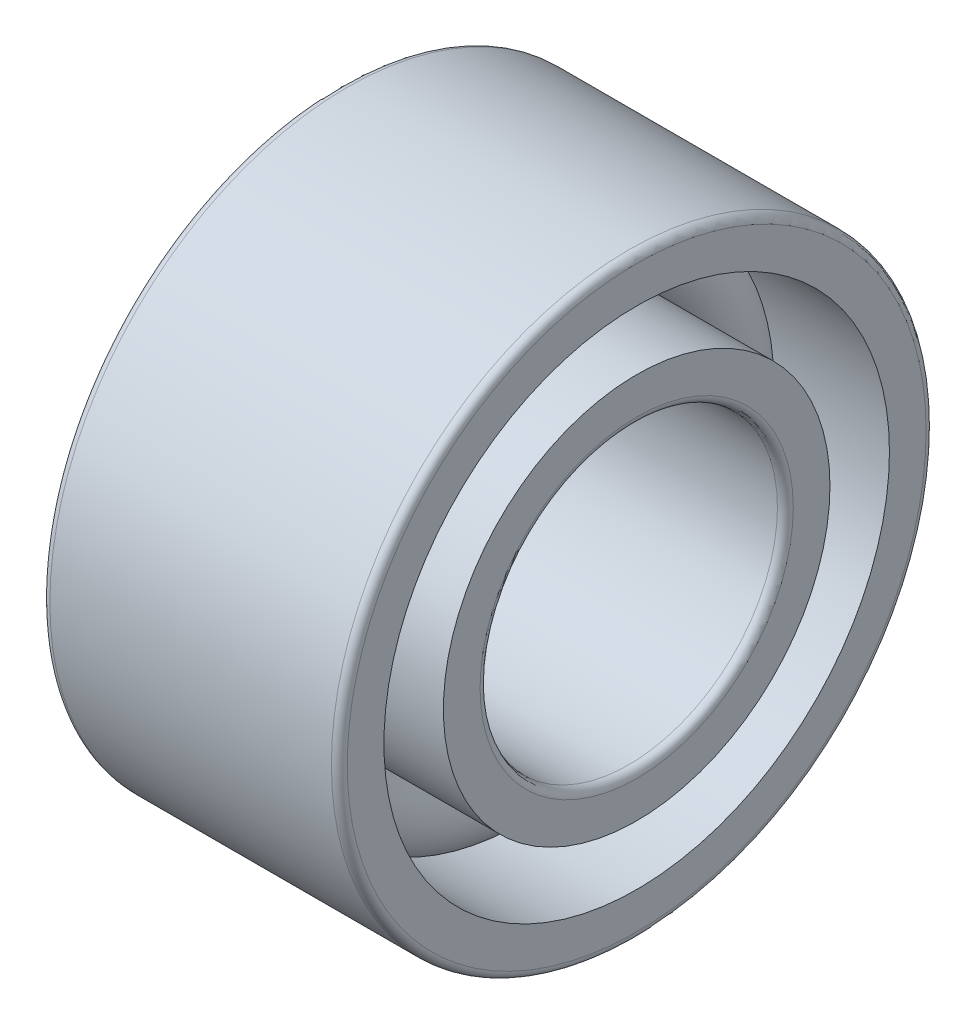
SolidWorks part; units mm, degrees
ref_plane "Plane1" through (0, 0, 0) normal (0, 0, 1) x (1, 0, 0)
ref_plane "Plane2" through (0, 0, 0) normal (0, 1, 0) x (1, 0, 0)
ref_plane "Plane3" through (0, 0, 0) normal (1, 0, 0) x (0, 0, -1)
other "Configuration Table"
sketch "Clipboard" plane through (0, 0, 0) normal (0, 0, 1) x (1, 0, 0)
  line L0 (-10, 0) -> (10, 0) construction
  line L1 (0, 0) -> (22.3471, -0.7804)
  line L2 (0, 0) -> (2.2486, 0.0785)
  line L3 (0, 0) -> (22.3471, -0.7804)
  line L4 (0, 0) -> (-22.3573, -0.3902)
  dimension "BallCLRad" = 2.25
sketch "CagSpiSke" plane through (0, 0, 0) normal (0, 0, 1) x (1, 0, 0)
  line L0 (0.045, 2.175) -> (0.045, 2.325)
  line L1 (0.045, 2.325) -> (-0.045, 2.325)
  line L2 (-0.045, 2.325) -> (-0.045, 2.175)
  line L3 (-0.045, 2.175) -> (0.045, 2.175)
  line L4 (-20.6375, 0) -> (20.6375, 0) construction
  line L5 (0, 0) -> (0, 23.7692) construction
  dimension "OD" = 4.65
  dimension "ID" = 4.35
revolve "CageSpine" add sketch "CagSpiSke" angle 0.001 about L4 reverse direction yes
ref_axis "Axis1" through (-50, 0, 0) along (1, 0, 0)
sketch "CagBalSke" plane through (0, 0, 0) normal (0, 0, 1) x (1, 0, 0)
  line L0 (-0.495, 2.25) -> (0.495, 2.25)
  line L1 (-1.905, 2.25) -> (1.905, 2.25) construction
  line L2 (-10, 0) -> (10, 0) construction
  line L3 (0, 0) -> (0, 24) construction
  arc A0 (0.495, 2.25) -> (-0.495, 2.25) centre (0, 2.25) cw
  dimension "BallCLRad" = 2.25
revolve "CageBall" [suppressed] add sketch "CagBalSke" angle 360 about L1 reverse direction yes
pattern_circular "CageBalls" [suppressed] count 2 every 180 about axis through (-50, 0, 0) along (1, 0, 0)
sketch "CagTrmODSke" plane through (0, 0, 0) normal (0, 0, 1) x (1, 0, 0)
  line L0 (0.496, 2.325) -> (0.496, 2.746)
  line L1 (0.496, 2.746) -> (-0.496, 2.746)
  line L2 (-0.496, 2.746) -> (-0.496, 2.325)
  line L3 (-0.496, 2.325) -> (0.496, 2.325)
  line L4 (-20.6375, 0) -> (20.6375, 0) construction
  line L5 (0, 0) -> (0, 25) construction
  dimension "Width" = 0.992
  dimension "ID" = 4.65
  dimension "OD" = 5.492
revolve "CageTrimOD" [suppressed] cut sketch "CagTrmODSke" angle 360 about L4 reverse direction yes
sketch "CagTrmIDSke" plane through (0, 0, 0) normal (0, 0, 1) x (1, 0, 0)
  line L0 (0.496, 1.756) -> (0.496, 2.175)
  line L1 (0.496, 2.175) -> (-0.496, 2.175)
  line L2 (-0.496, 2.175) -> (-0.496, 1.756)
  line L3 (-0.496, 1.756) -> (0.496, 1.756)
  line L4 (-20.6375, 0) -> (20.6375, 0) construction
  line L5 (0, 0) -> (0, 25) construction
  dimension "Width" = 0.992
  dimension "ID" = 3.512
  dimension "OD" = 4.35
revolve "CageTrimID" [suppressed] cut sketch "CagTrmIDSke" angle 360 about L4 reverse direction yes
sketch "BalSimSke" plane through (0, 0, 0) normal (0, 0, 1) x (1, 0, 0)
  line L0 (-10, 0) -> (10, 0) construction
  line L1 (-10, 2.25) -> (10, 2.25) construction
  line L2 (0, 0) -> (0, 23) construction
  circle A0 centre (0, 2.25) radius 0.45
  dimension "BallCLRad" = 2.25
  dimension "Ball_diameter" = 0.9
revolve "BallsSimplified" add sketch "BalSimSke" angle 360 about L0
sketch "BalDetSke" plane through (0, 0, 0) normal (0, 0, 1) x (1, 0, 0)
  line L0 (-0.45, 2.25) -> (0.45, 2.25)
  line L1 (-1.905, 2.25) -> (1.905, 2.25) construction
  line L2 (0, 0) -> (0, 25) construction
  arc A0 (0.45, 2.25) -> (-0.45, 2.25) centre (0, 2.25) cw
  dimension "BallCLRad" = 2.25
  dimension "Ball_diameter" = 0.9
revolve "BallDetailed" [suppressed] add sketch "BalDetSke" angle 360 about L1 reverse direction yes
sketch "InnRacSke" plane through (0, 0, 0) normal (0, 0, 1) x (1, 0, 0)
  line L0 (-0.301, 1.95) -> (-1.5, 1.95)
  line L1 (-1.5, 1.95) -> (-1.5, 1.58)
  line L2 (-1.42, 1.5) -> (1.42, 1.5)
  line L3 (1.5, 1.58) -> (1.5, 1.95)
  line L4 (1.5, 1.95) -> (0.301, 1.95)
  line L5 (-20.6375, 0) -> (20.6375, 0) construction
  line L6 (0, 0) -> (0, 30) construction
  arc A0 (-1.5, 1.58) -> (-1.42, 1.5) centre (-1.42, 1.58) ccw
  arc A1 (1.42, 1.5) -> (1.5, 1.58) centre (1.42, 1.58) ccw
  arc A2 (0.301, 1.95) -> (-0.301, 1.95) centre (0, 2.25) cw
  dimension "BallCLRad" = 2.25
  dimension "Fillet_radius" = 0.08
  dimension "Ball_diameter" = 0.85
  dimension "ID" = 3
  dimension "OD" = 3.9
  dimension "Width" = 3
revolve "InnerRace" add sketch "InnRacSke" angle 360 about L5 reverse direction yes
sketch "OutRacSke" plane through (0, 0, 0) normal (0, 0, 1) x (1, 0, 0)
  line L0 (-0.301, 2.55) -> (-1.5, 2.55)
  line L1 (-1.5, 2.55) -> (-1.5, 2.92)
  line L2 (-1.42, 3) -> (1.42, 3)
  line L3 (1.5, 2.92) -> (1.5, 2.55)
  line L4 (1.5, 2.55) -> (0.301, 2.55)
  line L5 (-20.6375, 0) -> (20.6375, 0) construction
  line L6 (0, 0) -> (0, 30) construction
  arc A0 (-1.5, 2.92) -> (-1.42, 3) centre (-1.42, 2.92) cw
  arc A1 (1.42, 3) -> (1.5, 2.92) centre (1.42, 2.92) cw
  arc A2 (0.301, 2.55) -> (-0.301, 2.55) centre (0, 2.25) ccw
  dimension "BallCLRad" = 2.25
  dimension "Fillet_radius" = 0.08
  dimension "Ball_diameter" = 0.85
  dimension "Width" = 3
revolve "OuterRace" add sketch "OutRacSke" angle 360 about L5 reverse direction yes
pattern_circular "BallsDetailed" [suppressed] count 2 every 180 about axis through (-50, 0, 0) along (1, 0, 0)
equation "\"BallCLRad@Clipboard\" = ( \"OD@OutRacSke\" + \"ID@InnRacSke\" ) / 4"
equation "\"BallCLRad@BalSimSke\" = \"BallCLRad@Clipboard\""
equation "\"BallCLRad@BalDetSke\" = \"BallCLRad@Clipboard\""
equation "\"BallCLRad@InnRacSke\" = \"BallCLRad@Clipboard\""
equation "\"BallCLRad@OutRacSke\" = \"BallCLRad@Clipboard\""
equation "\"Ball_diameter@InnRacSke\" = \"Ball_diameter@BalDetSke\" - 0.05"
equation "\"Ball_diameter@OutRacSke\" = \"Ball_diameter@BalDetSke\" - 0.05"
equation "\"Ball_diameter@BalSimSke\" = \"Ball_diameter@BalDetSke\""
equation "\"Width@OutRacSke\" = \"Width@InnRacSke\""
equation "\"Fillet_radius@OutRacSke\" = \"Fillet_radius@InnRacSke\""
equation "\"Max_count@Clipboard\" = int( 3.14159265 / atn(( \"Ball_diameter@BalDetSke\" / 2) / sqr( \"BallCLRad@Clipboard\"  *  \"BallCLRad@Clipboard\" - ( \"Ball_diameter@BalDetSke\" / 2) *  ( \"Ball_diameter@BalDetSke\" / 2))))"
equation "\"Max_count@Clipboard\" = ((sgn( \"Max_count@Clipboard\" - \"Count@Clipboard\" )-1)*( \"Max_count@Clipboard\" - \"Count@Clipboard\" ))/-2+ \"Count@Clipboard\""
equation "\"Count@BallsDetailed\" = int( \"Show_count@Clipboard\" ) "
equation "\"Count@BallsDetailed\" = ((sgn( \"Count@BallsDetailed\" - \"Max_count@Clipboard\" )-1)*( \"Count@BallsDetailed\" - \"Max_count@Clipboard\" ))/-2+ \"Max_count@Clipboard\""
equation "\"Count@BallsDetailed\" = ((sgn( \"Count@BallsDetailed\" - \"Min_count@Clipboard\" )+1)*( \"Count@BallsDetailed\" - \"Min_count@Clipboard\"))/2 +\"Min_count@Clipboard\""
equation "\"Angle@BallsDetailed\" = 360.0 / \"Max_count@Clipboard\""
equation "\"BallCLRad@CagBalSke\" = \"BallCLRad@Clipboard\""
equation "\"Count@CageBalls\" = \"Count@BallsDetailed\""
equation "\"Angle@CageBalls\" = \"Angle@BallsDetailed\""
equation "\"Angle@CageSpine\" =  \"Angle@CageBalls\" * ( \"Count@CageBalls\" -1 + int( \"Count@CageBalls\" / \"Max_count@Clipboard\" ) )  + 0.001 -  int( \"Count@CageBalls\" / \"Max_count@Clipboard\" ) * 0.001"
equation "\"Angle@CageSpine\" =  \"Angle@CageSpine\" * int( \"Min_count@Clipboard\" / 2) + int(1 / \"Min_count@Clipboard\")  * 0.001"
equation "\"CageWallOD@CagBalSke\" =  \"Ball_diameter@BalDetSke\" * 1.1"
equation "\"Thickness@CagSpiSke\" =  \"Ball_diameter@BalDetSke\" * 0.1"
equation "\"OD@CagTrmODSke\" = \"BallCLRad@Clipboard\" * 2 + \"CageWallOD@CagBalSke\" + 0.002"
equation "\"ID@CagTrmODSke\" = \"BallCLRad@Clipboard\" * 2 + \"Ball_diameter@BalDetSke\" / 6"
equation "\"OD@CagTrmIDSke\" = \"BallCLRad@Clipboard\" * 2 - \"Ball_diameter@BalDetSke\" / 6"
equation "\"ID@CagTrmIDSke\" = \"BallCLRad@Clipboard\" * 2 - \"CageWallOD@CagBalSke\" + 0.002"
equation "\"OD@CagSpiSke\" = \"ID@CagTrmODSke\""
equation "\"ID@CagSpiSke\" = \"OD@CagTrmIDSke\""
equation "\"Width@CagTrmODSke\" = \"CageWallOD@CagBalSke\" + 0.002"
equation "\"Width@CagTrmIDSke\" = \"CageWallOD@CagBalSke\" + 0.002"
